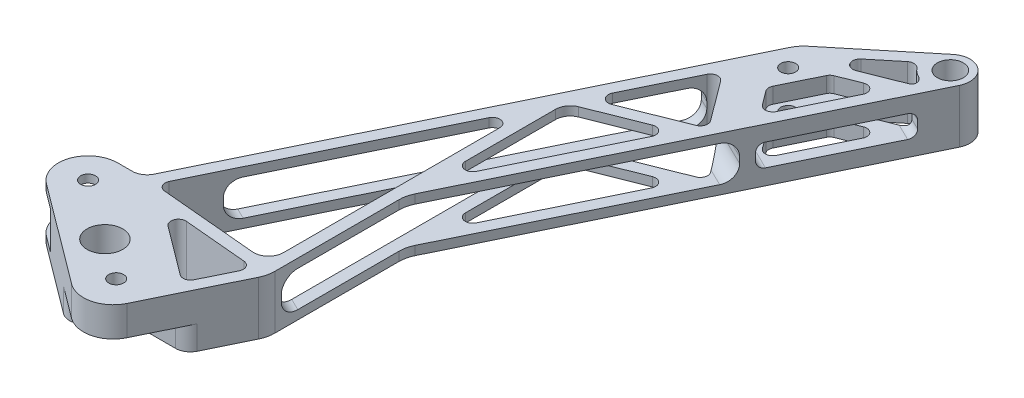
SolidWorks part; units mm, degrees
other "Markup1"
sketch "Sketch8" plane through (-93.2899, 0, 13.5035) normal (-0.9771, -0.046, 0.2078) x (0.0823, -0.982, 0.1697)
material "7075-T6 (SN)"
ref_plane "Front Plane" through (0, 0, 0) normal (0, 0, 1) x (1, 0, 0)
ref_plane "Top Plane" through (0, 0, 0) normal (0, 1, 0) x (1, 0, 0)
ref_plane "Right Plane" through (0, 0, 0) normal (1, 0, 0) x (0, 0, -1)
sketch "Sketch1" plane through (0, 0, 0) normal (0, 1, 0) x (1, 0, 0)
  line L2 (0, 0) -> (-80.5899, 0) construction
  line L3 (-80.5899, 0) -> (-80.5899, 19.05) construction
  line L5 (-80.5899, 31.75) -> (-93.2899, 31.75) construction
  line L6 (0, 0) -> (116.04, 82.2816) construction
  line L7 (0, 0) -> (236.4703, 0) construction
  line L8 (-80.5899, 31.75) -> (-80.5899, 44.45) construction
  line L10 (-80.5899, 44.45) -> (-70.4406, 44.45)
  line L11 (0, 0) -> (0, 222.7473) construction
  line L12 (0, 222.7473) -> (27.3244, 222.7473) construction
  line L13 (27.3244, 222.7473) -> (62.8844, 256.4224) construction
  line L14 (-70.4406, 44.45) -> (21.3976, 233.1226)
  line L15 (21.3976, 233.1226) -> (57.5832, 262.8707)
  line L21 (70.3901, 252.7689) -> (-6.9762, 93.8275)
  line L22 (-6.9762, 93.8275) -> (-6.9762, 34.9231)
  line L23 (-38.1, 0) -> (0, 0) construction
  line L24 (-26.6809, -5.5583) -> (-6.9762, 34.9231)
  line L25 (-45.702, -10.1735) -> (-88.1919, 21.5765)
  line L26 (-80.5899, 28.575) -> (-80.5899, 31.75) construction
  line L27 (-6.9762, 34.9231) -> (85.9158, 34.9231) construction
  line L28 (-38.1, 0) -> (-38.1, 1.27) construction
  circle A0 centre (0, 0) radius 13.2 construction
  circle A4 centre (-80.5899, 31.75) radius 3.175
  circle A6 centre (116.04, 82.2816) radius 99.9619 construction
  circle A7 centre (27.3244, 222.7473) radius 3.175
  circle A8 centre (62.8844, 256.4224) radius 5.5372
  arc A9 (70.3901, 252.7689) -> (57.5832, 262.8707) centre (62.8844, 256.4224) ccw
  arc A10 (-80.5899, 44.45) -> (-88.1919, 21.5765) centre (-80.5899, 31.75) ccw
  arc A11 (-45.702, -10.1735) -> (-26.6809, -5.5583) centre (-38.1, 0) ccw
  circle A12 centre (-38.1, 1.27) radius 3.175
  dimension "D1" = 26.4
  dimension "D3" = 38.1
  dimension "D4" = 1.27
  dimension "D7" = 6.35
  dimension "D11" = 199.9238
  dimension "D16" = 6.35
  dimension "D19" = 11.0744
  dimension "D20" = 16.6953
  dimension "D23" = 25.4
  dimension "D24" = 25.4
  dimension "D13" = 6.35
  dimension "D5" = 80.5899
  dimension "D6" = 31.75
  dimension "D8" = 12.7
  dimension "D9" = 142.2517
  dimension "D10" = 35.34
  dimension "D12" = 90
  dimension "D14" = 222.7473
  dimension "D15" = 27.3244
  dimension "D17" = 35.56
  dimension "D18" = 33.6751
  dimension "D21" = 209.8371
  dimension "D22" = 115.955
extrude "Boss-Extrude1" add sketch "Sketch1" along normal blind 22.86
ref_plane "Plane1" through (0, 11.43, 0) normal (0, -1, 0) x (-1, 0, 0)
sketch "Sketch2" plane through (0, 11.43, 0) normal (0, -1, 0) x (-1, 0, 0)
  line L0 (93.2899, 16.51) -> (119.1237, 16.51)
  line L2 (65.3499, 44.45) -> (65.3499, 16.51)
  line L3 (65.3499, 16.51) -> (93.2899, 16.51)
  line L5 (119.1237, 16.51) -> (119.1237, 65.6742)
  line L6 (119.1237, 65.6742) -> (65.3499, 65.6742)
  line L7 (65.3499, 65.6742) -> (65.3499, 44.45)
  line L8 (65.3499, 44.45) -> (93.2899, 44.45) construction
  line L9 (93.2899, 44.45) -> (93.2899, 16.51) construction
  dimension "D1" = 27.94
  dimension "D2" = 27.94
extrude "Cut-Extrude1" cut sketch "Sketch2" against normal mid plane 16.1199
ref_plane "Plane2" through (0, 0, 0) normal (0, -1, 0) x (-1, 0, 0)
sketch "Sketch4" plane through (0, 0, 0) normal (0, -1, 0) x (-1, 0, 0)
  line L0 (38.1, 11.049) -> (10.8954, 11.049)
  line L3 (13.0153, -21.2643) -> (10.8954, 11.049)
  line L4 (45.9336, 7.1235) -> (62.5249, -15.0801)
  line L5 (88.1919, 21.5765) -> (45.702, -10.1735) construction
  line L6 (13.0153, -21.2643) -> (62.5249, -15.0801)
  arc A0 (45.9336, 7.1235) -> (38.1, 11.049) centre (38.1, 1.27) ccw
  dimension "D1" = 19.558
extrude "Cut-Extrude2" cut sketch "Sketch4" against normal blind 10.16
sketch "Sketch7" plane through (0, 11.43, 0) normal (0, -1, 0) x (-1, 0, 0)
  line L0 (-30.6397, 213.1434) -> (66.2774, 179.6869)
  line L5 (-21.3976, 233.1226) -> (70.4406, 44.45) construction
  line L7 (16.7462, 250.5042) -> (66.2774, 179.6869)
  line L12 (-30.9579, 232.2353) -> (16.7462, 250.5042)
  arc A1 (-30.9579, 232.2353) -> (-30.6397, 213.1434) centre (-27.3244, 222.7473) ccw
  dimension "D1" = 40
  dimension "D3" = 10.16
  dimension "D2" = 45
sketch "Sketch9" plane through (0, 11.43, 0) normal (0, -1, 0) x (-1, 0, 0)
  line L0 (70.4406, 44.45) -> (182.9551, 44.45) construction
  line L1 (161.01, 44.45) -> (161.01, 78.0455) construction
  line L2 (161.01, 44.45) -> (114.9859, 62.7187) construction
  line L4 (-27.3244, 222.7473) -> (-61.6106, 236.3568) construction
  line L5 (80.5899, 31.75) -> (59.1069, 40.2774) construction
  line L6 (161.01, 44.45) -> (120.2127, 28.256) construction
  line L7 (161.01, 44.45) -> (161.01, 6.854) construction
  dimension "D1" = 68.35
  dimension "D2" = 21.65
  dimension "D3" = 68.35
sketch "Sketch10" plane through (0, 0, 0) normal (0, -1, 0) x (-1, 0, 0)
  line L0 (-14.647, 207.647) -> (4.4116, 168.4932)
  line L1 (4.4116, 168.4932) -> (-32.8321, 183.2766)
  line L2 (-32.8321, 183.2766) -> (-14.647, 207.647)
  line L3 (6.9762, 162.0096) -> (-27.1573, 175.5585)
  line L4 (-27.1573, 175.5585) -> (6.9762, 105.4345)
  line L5 (6.9762, 162.0096) -> (6.9762, 105.4345)
  line L6 (12.0562, 152.788) -> (12.0562, 39.689)
  line L7 (64.7908, 44.45) -> (12.0562, 152.788)
  line L8 (12.0562, 39.689) -> (64.7908, 44.45)
  line L9 (55.4982, 38.5104) -> (12.7582, 34.6517)
  line L10 (12.7582, 34.6517) -> (22.7802, 14.0623)
  line L11 (22.7802, 14.0623) -> (55.4982, 38.5104)
  line L12 (-21.3976, 233.1226) -> (70.4406, 44.45) construction
  line L13 (6.9762, 93.8275) -> (-70.3901, 252.7689) construction
  line L14 (-27.3244, 222.7473) -> (-61.6106, 236.3568) construction
  line L15 (-61.6121, 246.3424) -> (-59.9621, 242.9527)
  line L16 (-59.9621, 242.9527) -> (-23.9817, 228.6707)
  line L18 (-23.9817, 228.6707) -> (-53.3779, 252.8373)
  line L21 (-57.5832, 262.8707) -> (-21.3976, 233.1226) construction
  line L22 (18.5972, 11.049) -> (6.9762, 34.9231) construction
  line L23 (6.9762, 34.9231) -> (6.9762, 93.8275) construction
  line L24 (-199929.5594, 44.45) -> (200193.5629, 44.45) construction
  line L25 (88.1919, 21.5765) -> (54.1445, -3.8649) construction
  line L41 (-38.9055, 229.129) -> (-56.6646, 236.1782)
  line L43 (-56.6646, 236.1782) -> (-38.7051, 199.2822)
  line L44 (38.1, 1.27) -> (80.5899, 31.75) construction
  line L45 (-38.7051, 199.2822) -> (-30.0338, 210.9029)
  line L46 (-30.0338, 210.9029) -> (-38.9055, 229.129)
  arc A0 (-61.6121, 246.3424) -> (-53.3779, 252.8373) centre (-62.8844, 256.4224) ccw construction
  arc A1 (-61.6121, 246.3424) -> (-53.3779, 252.8373) centre (-62.8844, 256.4224) ccw
  circle A2 centre (-27.3244, 222.7473) radius 3.175 construction
  circle A5 centre (55.1573, 13.506) radius 7.62
  point P44 (-58.7435, 240.4492)
  point P45 (-40.2022, 231.7929)
  point P48 (-59.8816, 242.7872)
  point P49 (-24.1494, 228.6707)
  dimension "D11" = 20.32
  dimension "D15" = 5.08
  dimension "D13" = 15.24
  dimension "D17" = 7.62
  dimension "D1" = 5.08
  dimension "D2" = 5.08
  dimension "D3" = 5.08
  dimension "D4" = 5.08
  dimension "D5" = 5.08
  dimension "D6" = 5.08
  dimension "D7" = 5.08
  dimension "D8" = 5.08
  dimension "D9" = 5.08
  dimension "D10" = 5.08
  dimension "D12" = 5.08
  dimension "D14" = 5.08
  dimension "D16" = 14.2791
extrude "Cut-Extrude4" cut sketch "Sketch10" against normal through all both and the other way through all
fillet "Fillet1" radius 3.175 18 edges at (-55.4982, 11.43, -38.5104) (-12.7582, 11.43, -34.6517) (27.1573, 11.43, -175.5585) (14.647, 11.43, -207.647) (32.8321, 11.43, -183.2766) (-4.4116, 11.43, -168.4932) (-22.7802, 11.43, -14.0623) (-64.7908, 11.43, -44.45) (59.9621, 11.43, -242.9527) (38.7051, 11.43, -199.2822) (30.0338, 11.43, -210.9029) (56.6646, 11.43, -236.1782) (38.9055, 11.43, -229.129)
fillet "Fillet2" radius 12.7 3 edges at (21.3976, 11.43, -233.1226) (-6.9762, 11.43, -93.8275) (-6.9762, 11.43, -34.9231)
sketch "Sketch11" plane through (-74.4397, 0, -36.2343) normal (-0.8991, 0, -0.4377) x (-0.4377, 0, 0.8991)
  line L0 (-216.2029, 22.86) -> (-9.1373, 22.86) construction
  line L1 (-187.9006, 19.05) -> (-33.4689, 19.05)
  line L2 (-187.9006, 19.05) -> (-187.9006, 3.81)
  line L3 (-187.9006, 3.81) -> (-33.4689, 3.81)
  line L4 (-33.4689, 19.05) -> (-33.4689, 3.81)
  line L5 (-216.2029, 0) -> (-9.1373, 0) construction
  line L6 (-20.7689, 3.3701) -> (-20.7689, 19.4899) construction
  line L7 (-187.9006, 0) -> (-187.9006, 22.86) construction
  dimension "D1" = 3.81
  dimension "D2" = 3.81
  dimension "D4" = 12.7
extrude "Cut-Extrude5" cut sketch "Sketch11" against normal blind 111.76
fillet "Fillet5" radius 6.35 9 edges at (-57.5078, 19.05, -65.2158) (-57.5078, 3.81, -65.2158) (10.0815, 19.05, -204.0713) (10.0815, 3.81, -204.0713) (30.5578, 19.05, -194.1042) (30.5578, 3.81, -194.1042) (-12.0562, 11.43, -39.689) (-6.9762, 20.955, -162.0096) (-6.9762, 1.905, -162.0096)
sketch "Sketch12" plane through (-74.4397, 0, -36.2343) normal (-0.8991, 0, -0.4377) x (-0.4377, 0, 0.8991)
  line L0 (-216.2029, 22.86) -> (-9.1373, 22.86) construction
  line L1 (-244.7468, 16.1925) -> (-192.9806, 16.1925)
  line L2 (-244.7468, 16.1925) -> (-244.7468, 6.6675)
  line L3 (-244.7468, 6.6675) -> (-192.9806, 6.6675)
  line L4 (-192.9806, 16.1925) -> (-192.9806, 6.6675)
  line L5 (-187.9006, 12.7) -> (-187.9006, 10.16) construction
  line L7 (-261.5593, 22.86) -> (-261.5593, 0) construction
  dimension "D1" = 9.525
  dimension "D2" = 6.6675
  dimension "D3" = 5.08
  dimension "D4" = 16.8125
extrude "Cut-Extrude6" cut sketch "Sketch12" against normal blind 43.18
fillet "Fillet8" radius 6.35 1 edges at (-54.1445, 5.08, 3.8649)
fillet "Fillet7" radius 6.35 6 edges at (-18.5972, 5.08, -11.049) (-70.4406, 1.685, -44.45) (-70.4406, 21.175, -44.45) (-9.932, 19.05, -42.0578) (-9.932, 3.81, -42.0578) (-65.3499, 11.43, -16.51)
fillet "Fillet4" radius 3.175 6 edges at (62.1687, 6.6675, -241.9403) (62.1687, 16.1925, -241.9403) (45.8093, 6.6675, -249.9033) (45.8093, 16.1925, -249.9033) (25.9594, 6.6675, -201.9924) (25.9594, 16.1925, -201.9924)
